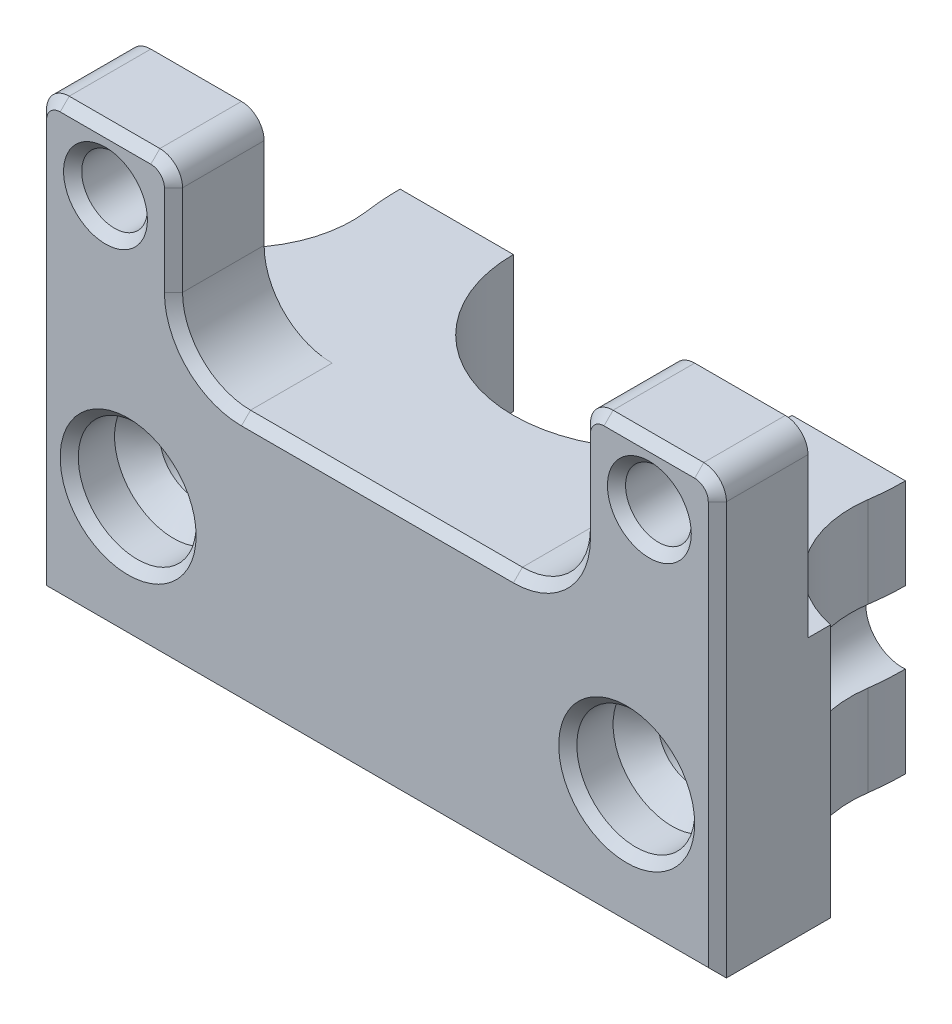
SolidWorks part; units mm, degrees
ref_plane "前视基准面" through (0, 0, 0) normal (0, 0, 1) x (1, 0, 0)
ref_plane "上视基准面" through (0, 0, 0) normal (0, 1, 0) x (1, 0, 0)
ref_plane "右视基准面" through (0, 0, 0) normal (1, 0, 0) x (0, 0, -1)
other "Configuration Table"
sketch "草图1" plane through (0, 0, 0) normal (0, 1, 0) x (1, 0, 0)
  line L0 (-11.15, 0) -> (-8.15, 0)
  line L1 (8.15, 0) -> (11.15, 0)
  arc A0 (-8.15, 0) -> (8.15, 0) centre (0, 0) ccw
  arc A1 (-11.15, 0) -> (11.15, 0) centre (0, 0) ccw
  circle A3 centre (0, 0) radius 11.15 construction
  circle A4 centre (0, 0) radius 8.15 construction
  point P4 (7.7939, 2.3828)
  point P7 (11.15, 0)
  dimension "D1" = 16.3
  dimension "D2" = 3
extrude "凸台-拉伸1" add sketch "草图1" along normal blind 5.2
sketch "草图2" plane through (0, 5.2, 0) normal (0, 1, 0) x (1, 0, 0)
  line L0 (-11.15, 0) -> (-6.15, 0)
  line L1 (6.15, 0) -> (11.15, 0)
  arc A0 (-11.15, 0) -> (11.15, 0) centre (0, 0) ccw
  arc A1 (-6.15, 0) -> (6.15, 0) centre (0, 0) ccw
  dimension "D1" = 12.3
extrude "凸台-拉伸2" add sketch "草图2" along normal blind 6
sketch "草图3" plane through (0, 11.2, 0) normal (0, 1, 0) x (1, 0, 0)
  line L0 (3.9115, -7.15) -> (15, -7.15)
  line L1 (-15, -7.15) -> (-3.9115, -7.15)
  line L2 (-15, -7.15) -> (-15, -11.15)
  line L3 (-15, -11.15) -> (15, -11.15)
  line L4 (15, -7.15) -> (15, -11.15)
  arc A0 (-11.15, 0) -> (11.15, 0) centre (0, 0) ccw construction
  arc A1 (-3.9115, -7.15) -> (3.9115, -7.15) centre (0, 0) ccw
  point P7 (0, -11.15)
  dimension "D1" = 11.15
  dimension "D2" = 30
  dimension "D3" = 0
  dimension "D4" = 4
extrude "凸台-拉伸3" add sketch "草图3" against normal up to surface (11.2 mm away) up to face at (0, 0, 4.825)
fillet "圆角1" radius 5 2 edges at (-8.5557, 5.6, 7.15) (8.5557, 5.6, 7.15)
sketch "草图4" plane through (0, 0, 11.15) normal (0, 0, 1) x (1, 0, 0)
  line L0 (-15, 0) -> (-15, 11.2) construction
  line L1 (15, 0) -> (15, 11.2) construction
  line L2 (-15, 11.2) -> (15, 11.2) construction
  circle A0 centre (-11, 5.6) radius 1.6
  circle A1 centre (11, 5.6) radius 1.6
  point P6 (-15, 5.6)
  point P9 (15, 5.6)
  point P12 (0, 11.2)
  dimension "D1" = 3.2
  dimension "D2" = 3.2
  dimension "D3" = 0
  dimension "D4" = 0
  dimension "D5" = 11
  dimension "D6" = 11
extrude "切除-拉伸1" cut sketch "草图4" against normal through all
sketch "草图7" plane through (0, 11.2, 0) normal (0, 1, 0) x (1, 0, 0)
  line L1 (-15, -11.15) -> (-9, -11.15)
  line L2 (-15, -11.15) -> (-15, -8.15)
  line L3 (-15, -8.15) -> (-9, -8.15)
  line L4 (-9, -11.15) -> (-9, -8.15)
  line L5 (15, -11.15) -> (9, -11.15)
  line L6 (15, -11.15) -> (15, -8.15)
  line L7 (15, -8.15) -> (9, -8.15)
  line L8 (9, -11.15) -> (9, -8.15)
  dimension "D1" = 3
  dimension "D2" = 3
  dimension "D3" = 6
  dimension "D4" = 6
extrude "凸台-拉伸5" add sketch "草图7" along normal blind 8
sketch "草图8" plane through (0, 0, 11.15) normal (0, 0, 1) x (1, 0, 0)
  line L0 (-15, 0) -> (-15, 19.2) construction
  circle A0 centre (-12, 16.6) radius 1.45
  circle A1 centre (12, 16.6) radius 1.45
  circle A2 centre (-11, 5.6) radius 1.6 construction
  circle A3 centre (11, 5.6) radius 1.6 construction
  dimension "D1" = 2.9
  dimension "D2" = 2.9
  dimension "D3" = 24
  dimension "D4" = 11
  dimension "D5" = 11
  dimension "D6" = 3
extrude "切除-拉伸3" cut sketch "草图8" against normal blind 8
sketch "草图9" plane through (0, 0, 11.15) normal (0, 0, 1) x (1, 0, 0)
  line L16 (-15, 19.2) -> (-15, 0)
  line L17 (-15, 0) -> (15, 0)
  line L18 (15, 0) -> (15, 19.2)
  line L19 (15, 19.2) -> (9, 19.2)
  line L20 (9, 19.2) -> (9, 11.2)
  line L21 (9, 11.2) -> (-9, 11.2)
  line L22 (-9, 11.2) -> (-9, 19.2)
  line L23 (-9, 19.2) -> (-15, 19.2)
  line L24 (-15, 19.2) -> (-15, 0)
  line L25 (-15, 0) -> (15, 0)
  line L26 (15, 0) -> (15, 19.2)
  line L27 (15, 19.2) -> (9, 19.2)
  line L28 (9, 19.2) -> (9, 11.2)
  line L29 (9, 11.2) -> (-9, 11.2)
  line L30 (-9, 11.2) -> (-9, 19.2)
  line L31 (-9, 19.2) -> (-15, 19.2)
  circle A0 centre (-12, 16.6) radius 1.45
  circle A1 centre (-11, 5.6) radius 1.6
  circle A2 centre (11, 5.6) radius 1.6
  circle A3 centre (12, 16.6) radius 1.45
  dimension "D1" = 0
extrude "凸台-拉伸6" add sketch "草图9" along normal blind 1
fillet "圆角2" radius 3 2 edges at (9, 11.2, 10.15) (-9, 11.2, 10.15)
fillet "圆角3" radius 1 4 edges at (15, 19.2, 10.15) (9, 19.2, 10.15) (-9, 19.2, 10.15) (-15, 19.2, 10.15)
sketch "草图10" plane through (0, 0, 12.15) normal (0, 0, 1) x (1, 0, 0)
  circle A0 centre (11, 5.6) radius 2.6
  circle A1 centre (-11, 5.6) radius 2.6
  dimension "D1" = 5.2
  dimension "D2" = 5.2
extrude "切除-拉伸4" cut sketch "草图10" against normal blind 3
chamfer "倒角2" distance 1 angle 45 2 edges at (13.6, 5.6, 9.15) (-8.4, 5.6, 9.15)
chamfer "倒角1" distance 0.4 angle 45 18 edges at (13.45, 16.6, 12.15) (0, 0, 12.15) (-15, 9.1, 12.15) (-14.7071, 18.9071, 12.15) (-12, 19.2, 12.15) (-9.2929, 18.9071, 12.15) (-9, 16.2, 12.15) (-8.1213, 12.0787, 12.15) (0, 11.2, 12.15) (8.1213, 12.0787, 12.15) (9, 16.2, 12.15) (9.2929, 18.9071, 12.15) (12, 19.2, 12.15) (14.7071, 18.9071, 12.15) (15, 9.1, 12.15) (-10.55, 16.6, 12.15) (-8.4, 5.6, 12.15) (13.6, 5.6, 12.15)
equation "\"D1@草图3\"=22.3/2"
equation "\"D5@草图8\"=\"D4@草图8\""
